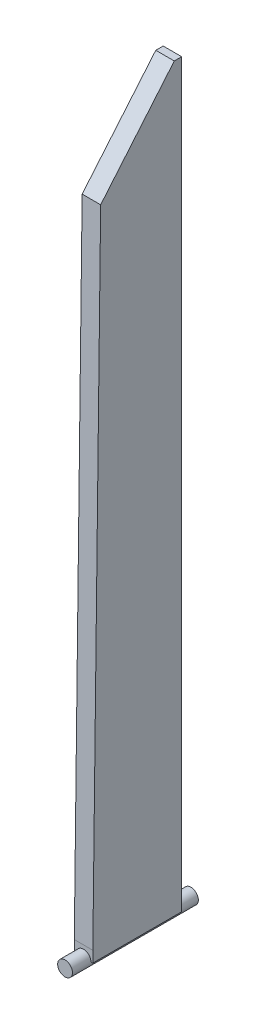
SolidWorks part; units mm, degrees
material "ABS"
ref_plane "Front Plane" through (0, 0, 0) normal (0, 0, 1) x (1, 0, 0)
ref_plane "Top Plane" through (0, 0, 0) normal (0, 1, 0) x (1, 0, 0)
ref_plane "Right Plane" through (0, 0, 0) normal (1, 0, 0) x (0, 0, -1)
ref_axis "Axis X" through (57.4134, 0, 0) along (-1, 0, 0)
ref_axis "Axis Y" through (0, 65.1338, 0) along (0, -1, 0)
ref_axis "Axis Z" through (0, 0, -90.83) along (0, 0, 1)
sketch "Sketch1" plane through (0, 0, 0) normal (0, 0, 1) x (1, 0, 0)
  line L0 (55, 0) -> (-55, 0) construction
  line L1 (-0.25, 0) -> (0.25, 0)
  line L2 (-0.25, 0) -> (-0.25, 20)
  line L3 (-0.25, 20) -> (0.25, 20)
  line L4 (0.25, 0) -> (0.25, 20)
  point P6 (0, 0)
  dimension "D1" = 0.5
  dimension "D2" = 20
extrude "Boss-Extrude1" add sketch "Sketch1" along normal blind 2.4
sketch "Sketch2" plane through (0, 0, 2.4) normal (0, 0, 1) x (1, 0, 0)
  circle A0 centre (0, 0) radius 0.2
  dimension "D1" = 0.4
extrude "Boss-Extrude2" add sketch "Sketch2" along normal blind 0.5 and the other way blind 2.9
sketch "Sketch3" plane through (0.25, 0, 0) normal (1, 0, 0) x (0, 0, -1)
  line L0 (-2.4, 0.3) -> (-3.1301, 0.3)
  line L1 (-3.1301, 0.3) -> (-3.1301, 41.7058)
  line L2 (-3.1301, 41.7058) -> (-0.2, 41.7058)
  line L3 (-0.2, 41.7058) -> (-0.2, 20)
  line L4 (-2.4, 20) -> (0, 20) construction
  line L5 (-0.2, 20) -> (-2.1883, 17.6305)
  line L6 (-2.1883, 17.6305) -> (-2.4, 0.3)
  line L7 (-2.4, 0) -> (-2.4, 20) construction
  line L8 (0, 0) -> (0, 20) construction
  dimension "D1" = 0.3
  dimension "D2" = 0.2
  dimension "D3" = 50
  dimension "D4" = 0.7
extrude "Cut-Extrude1" cut sketch "Sketch3" against normal up to next
